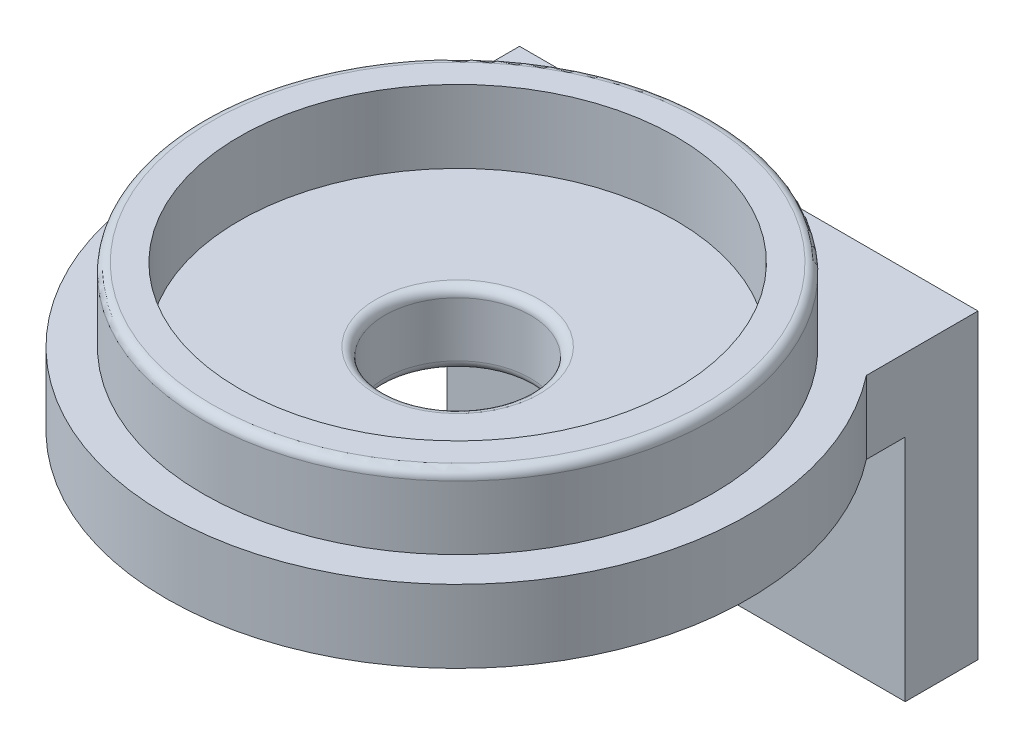
SolidWorks part; units mm, degrees
material "PLA Black"
ref_plane "Front Plane" through (0, 0, 0) normal (0, 0, 1) x (1, 0, 0)
ref_plane "Top Plane" through (0, 0, 0) normal (0, 1, 0) x (1, 0, 0)
ref_plane "Right Plane" through (0, 0, 0) normal (1, 0, 0) x (0, 0, -1)
sketch "Sketch1" plane through (0, 0, 0) normal (1, 0, 0) x (0, 0, -1)
  line L0 (0, -32.3252) -> (0, 32.3252) construction
  line L1 (22.225, 9.525) -> (22.225, 3.175)
  line L2 (22.225, 3.175) -> (25.4, 3.175)
  line L3 (25.4, 3.175) -> (25.4, -3.175)
  line L8 (19.05, 9.525) -> (22.225, 9.525)
  line L13 (19.05, 3.175) -> (19.05, 9.525)
  line L14 (19.05, 3.175) -> (6.35, 3.175)
  line L15 (6.35, 3.175) -> (6.35, -3.175)
  line L16 (6.35, -3.175) -> (25.4, -3.175)
  point P4 (0, 0)
  point P12 (25.4, 0)
  dimension "D1" = 3.175
  dimension "D2" = 6.35
  dimension "D3" = 6.35
  dimension "D4" = 50.8
  dimension "D5" = 12.7
revolve "Revolve1" add sketch "Sketch1" angle 360 about L0
fillet "Fillet1" radius 0.7937 3 edges at (0, 9.525, -22.225) (0, -3.175, -6.35) (0, 3.175, -6.35)
sketch "Sketch2" plane through (0, 0, 0) normal (1, 0, 0) x (0, 0, -1)
  line L0 (-25.4, -3.175) -> (25.4, -3.175) construction
  line L1 (25.4, 3.175) -> (12.7, 3.175)
  line L2 (25.4, 3.175) -> (25.4, -3.175)
  line L3 (19.05, -3.175) -> (12.7, -3.175)
  line L4 (12.7, 3.175) -> (12.7, -3.175)
  line L5 (25.4, 3.175) -> (12.7, -3.175) construction
  line L6 (25.4, -3.175) -> (12.7, 3.175) construction
  line L9 (25.4, -3.175) -> (25.4, -23.175)
  line L10 (25.4, -23.175) -> (19.05, -23.175)
  line L11 (19.05, -3.175) -> (19.05, -23.175)
  line L12 (25.4, -3.175) -> (19.05, -23.175) construction
  line L13 (25.4, -23.175) -> (19.05, -3.175) construction
  point P4 (19.05, 0)
  point P11 (22.225, -13.175)
  dimension "D1" = 12.7
  dimension "D2" = 20
  dimension "D3" = 6.35
extrude "Boss-Extrude1" add sketch "Sketch2" along normal mid plane 40
sketch "Sketch3" plane through (0, 0, -19.05) normal (0, 0, 1) x (1, 0, 0)
  arc A0 (-10, -15.275) -> (-10, -11.075) centre (-10, -13.175) ccw construction
  arc A1 (10, -15.275) -> (10, -11.075) centre (10, -13.175) ccw construction
  arc A2 (-10, -15.275) -> (-10, -11.075) centre (-10, -13.175) ccw
  arc A3 (10, -15.275) -> (10, -11.075) centre (10, -13.175) ccw
  circle A4 centre (-10, -13.175) radius 2.1
  circle A5 centre (10, -13.175) radius 2.1
extrude "Cut-Extrude1" cut sketch "Sketch3" against normal through all contours A2 A4 | A3 A5 region at (-10, -13.175, -19.05) region at (10, -13.175, -19.05)
